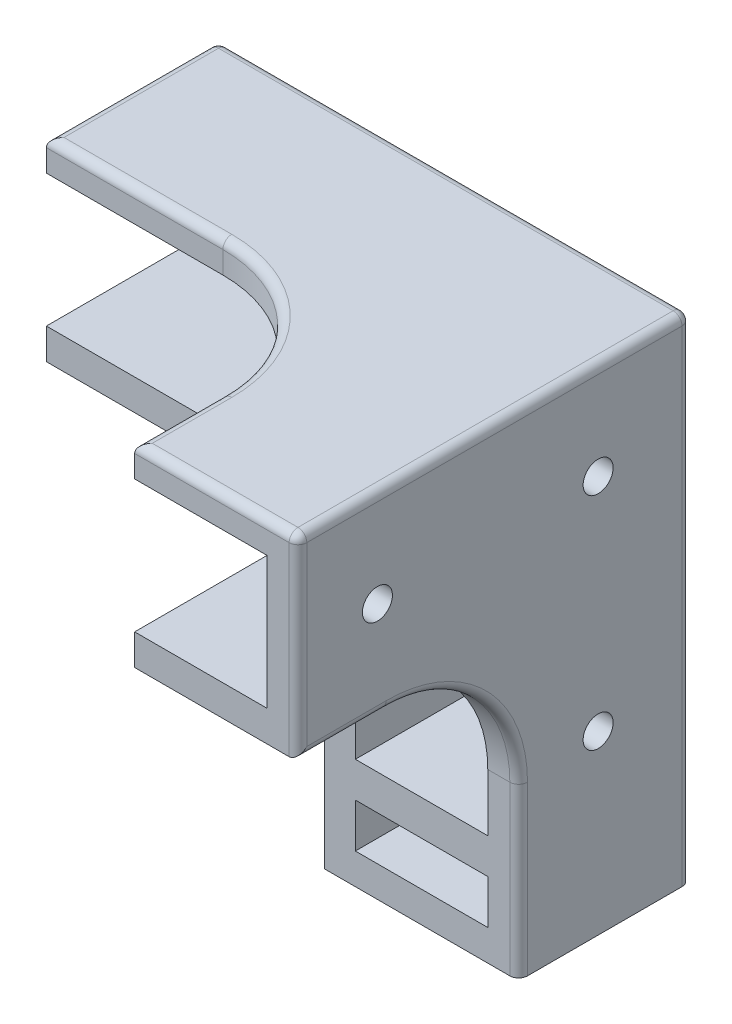
SolidWorks part; units mm, degrees
ref_plane "Front Plane" through (0, 0, 0) normal (0, 0, 1) x (1, 0, 0)
ref_plane "Top Plane" through (0, 0, 0) normal (0, 1, 0) x (1, 0, 0)
ref_plane "Right Plane" through (0, 0, 0) normal (1, 0, 0) x (0, 0, -1)
sketch "Sketch1" plane through (0, 0, 0) normal (0, 0, 1) x (1, 0, 0)
  line L1 (-5.6994, 32.9163) -> (16.3006, 32.9163)
  line L2 (-5.6994, 10.9163) -> (-5.6994, -23.0837)
  line L3 (-5.6994, -23.0837) -> (16.3006, -23.0837)
  line L4 (16.3006, 32.9163) -> (16.3006, -23.0837)
  line L5 (-5.6994, 10.9163) -> (-37.1994, 10.9163)
  line L7 (-5.6994, 32.9163) -> (-37.1994, 32.9163)
  line L8 (-37.1994, 10.9163) -> (-37.1994, 32.9163)
  dimension "D1" = 22
  dimension "D2" = 22
  dimension "D3" = 56
  dimension "D4" = 53.5
extrude "Boss-Extrude1" add sketch "Sketch1" along normal blind 19.5
sketch "Sketch3" plane through (0, 0, 19.5) normal (0, 0, 1) x (1, 0, 0)
  line L1 (16.3006, 32.9163) -> (-2.1994, 32.9163)
  line L2 (16.3006, 32.9163) -> (16.3006, 10.9163)
  line L3 (16.3006, 10.9163) -> (-2.1994, 10.9163)
  line L4 (-2.1994, 32.9163) -> (-2.1994, 10.9163)
  dimension "D1" = 18.5
  dimension "D2" = 22
extrude "Boss-Extrude2" add sketch "Sketch3" along normal blind 25
sketch "Sketch5" plane through (0, 0, 44.5) normal (0, 0, 1) x (1, 0, 0)
  line L0 (-37.1994, 32.9163) -> (-37.1994, 10.9163) construction
  line L1 (-37.1994, 29.4163) -> (12.8006, 29.4163)
  line L2 (-37.1994, 29.4163) -> (-37.1994, 14.4163)
  line L3 (-37.1994, 14.4163) -> (12.8006, 14.4163)
  line L4 (12.8006, 29.4163) -> (12.8006, 14.4163)
  line L5 (16.3006, 10.9163) -> (16.3006, 32.9163) construction
  line L6 (-2.1994, 4.4163) -> (12.8006, 4.4163)
  line L7 (-2.1994, 4.4163) -> (-2.1994, -10.5837)
  line L8 (-2.1994, -10.5837) -> (12.8006, -10.5837)
  line L9 (12.8006, 4.4163) -> (12.8006, -10.5837)
  line L12 (-2.1994, 32.9163) -> (-37.1994, 32.9163) construction
  line L13 (-2.1994, 10.9163) -> (16.3006, 10.9163) construction
  line L15 (16.3006, -23.0837) -> (16.3006, 10.9163) construction
  line L16 (-5.6994, -23.0837) -> (16.3006, -23.0837) construction
  line L17 (-2.1994, -14.5837) -> (12.8006, -14.5837)
  line L18 (-2.1994, -14.5837) -> (-2.1994, -19.5837)
  line L19 (-2.1994, -19.5837) -> (12.8006, -19.5837)
  line L20 (12.8006, -14.5837) -> (12.8006, -19.5837)
  dimension "D1" = 3.5
  dimension "D2" = 6.5
  dimension "D3" = 15
  dimension "D4" = 3.5
  dimension "D5" = 15
  dimension "D6" = 15
  dimension "D7" = 3.5
  dimension "D8" = 15
  dimension "D9" = 4
  dimension "D10" = 3.5
extrude "Cut-Extrude1" cut sketch "Sketch5" against normal offset from surface (40.5 mm away) 4 up to face at (-8.8661, 6.9163, 0)
sketch "Sketch7" plane through (16.3006, 0, 0) normal (1, 0, 0) x (0, 0, -1)
  line L0 (-34.5, 10.9163) -> (-19.5, 10.9163)
  line L1 (-44.5, 10.9163) -> (-19.5, 10.9163) construction
  line L2 (-19.5, 10.9163) -> (-19.5, -4.0837)
  line L3 (-19.5, -23.0837) -> (-19.5, 10.9163) construction
  arc A0 (-34.5, 10.9163) -> (-19.5, -4.0837) centre (-34.5, -4.0837) cw
  dimension "D1" = 15
extrude "Boss-Extrude4" add sketch "Sketch7" against normal blind 3.5
sketch "Sketch8" plane through (0, 0, 0) normal (0, 0, -1) x (-1, 0, 0)
  line L0 (5.6994, 10.9163) -> (20.6994, 10.9163)
  line L1 (37.1994, 10.9163) -> (5.6994, 10.9163) construction
  line L2 (5.6994, 10.9163) -> (5.6994, -4.0837)
  line L3 (5.6994, 10.9163) -> (5.6994, -23.0837) construction
  arc A0 (20.6994, 10.9163) -> (5.6994, -4.0837) centre (20.6994, -4.0837) ccw
  dimension "D1" = 15
extrude "Boss-Extrude5" add sketch "Sketch8" against normal blind 3.5
sketch "Sketch9" plane through (0, 32.9163, 0) normal (0, 1, 0) x (1, 0, 0)
  line L0 (-2.1994, -34.5) -> (-2.1994, -19.5)
  line L1 (-2.1994, -44.5) -> (-2.1994, -19.5) construction
  line L2 (-2.1994, -19.5) -> (-17.1994, -19.5)
  line L3 (-2.1994, -19.5) -> (-37.1994, -19.5) construction
  arc A0 (-2.1994, -34.5) -> (-17.1994, -19.5) centre (-17.1994, -34.5) ccw
  dimension "D1" = 15
extrude "Boss-Extrude6" add sketch "Sketch9" against normal blind 3.5
fillet "Fillet3" radius 3 1 edges
sketch "Sketch11" plane through (0, 0, 0) normal (0, 0, -1) x (-1, 0, 0)
  line L0 (1.1994, -23.0837) -> (1.1994, 10.9163) construction
  line L2 (5.6994, -23.0837) -> (-16.3006, -23.0837) construction
  line L5 (5.6994, -4.0837) -> (5.6994, -23.0837) construction
  text T0 "MR.3" font "Century Gothic" height 12
  dimension "D1" = 4.5
extrude "Cut-Extrude3" cut sketch "Sketch11" against normal blind 1
sketch "Sketch12" plane through (0, 0, 0) normal (0, 0, -1) x (-1, 0, 0)
  line L0 (37.1994, 21.9163) -> (-16.3006, 21.9163) construction
  line L1 (37.1994, 32.9163) -> (37.1994, 10.9163) construction
  line L2 (-16.3006, -23.0837) -> (-16.3006, 32.9163) construction
  line L3 (-12.8006, 14.4163) -> (-12.8006, 29.4163) construction
  circle A0 centre (-5.3006, 21.9163) radius 1.7
  circle A1 centre (10.9494, 21.9163) radius 1.7
  circle A2 centre (27.1994, 21.9163) radius 1.7
  dimension "D4" = 3.4
  dimension "D1" = 7.5
  dimension "D2" = 10
  dimension "D3" = 16.25
extrude "Cut-Extrude4" cut sketch "Sketch12" against normal blind 5
sketch "Sketch13" plane through (-5.6994, 0, 0) normal (-1, 0, 0) x (0, 0, 1)
  line L0 (4, 4.4163) -> (19.5, 4.4163) construction
  line L1 (19.5, 10.9163) -> (19.5, -23.0837) construction
  circle A0 centre (10.5, -3.0837) radius 1.7
  dimension "D2" = 9
  dimension "D3" = 3.4
  dimension "D1" = 7.5
extrude "Cut-Extrude5" cut sketch "Sketch13" against normal blind 45
sketch "Sketch14" plane through (16.3006, 0, 0) normal (1, 0, 0) x (0, 0, -1)
  line L0 (-10.5, -3.0837) -> (-10.5, 32.9163) construction
  line L1 (-44.5, 32.9163) -> (0, 32.9163) construction
  line L2 (-44.5, 21.9163) -> (-10.5, 21.9163) construction
  line L3 (-44.5, 10.9163) -> (-44.5, 32.9163) construction
  circle A0 centre (-10.5, 21.9163) radius 1.7
  circle A1 centre (-35.5, 21.9163) radius 1.7
  dimension "D1" = 3.4
  dimension "D2" = 9
extrude "Cut-Extrude6" cut sketch "Sketch14" against normal blind 45
sketch "Sketch15" plane through (0, -23.0837, 0) normal (0, -1, 0) x (1, 0, 0)
  line L0 (16.3006, 9.75) -> (-5.6994, 9.75) construction
  line L1 (16.3006, 19.5) -> (16.3006, 0) construction
  line L2 (-5.6994, 19.5) -> (-5.6994, 0) construction
  line L3 (5.3006, 19.5) -> (5.3006, 0) construction
  line L4 (-5.6994, 19.5) -> (16.3006, 19.5) construction
  line L5 (-5.6994, 0) -> (16.3006, 0) construction
  circle A0 centre (5.3006, 9.75) radius 1.7
  dimension "D1" = 3.4
extrude "Cut-Extrude7" cut sketch "Sketch15" against normal blind 4
fillet "Fillet4" radius 1 16 edges at (-28.9494, 10.9163, 0) (-10.0928, 6.5229, 0) (16.3006, 6.5229, 23.8934) (-6.5928, 32.9163, 23.8934) (-37.1994, 21.9163, 0) (-5.6994, -13.5837, 0) (-37.1994, 32.9163, 9.75) (-10.4494, 32.9163, 0) (7.0506, 32.9163, 44.5) (16.3006, 21.9163, 44.5) (16.3006, 32.9163, 22.25) (16.3006, 4.9163, 0)
